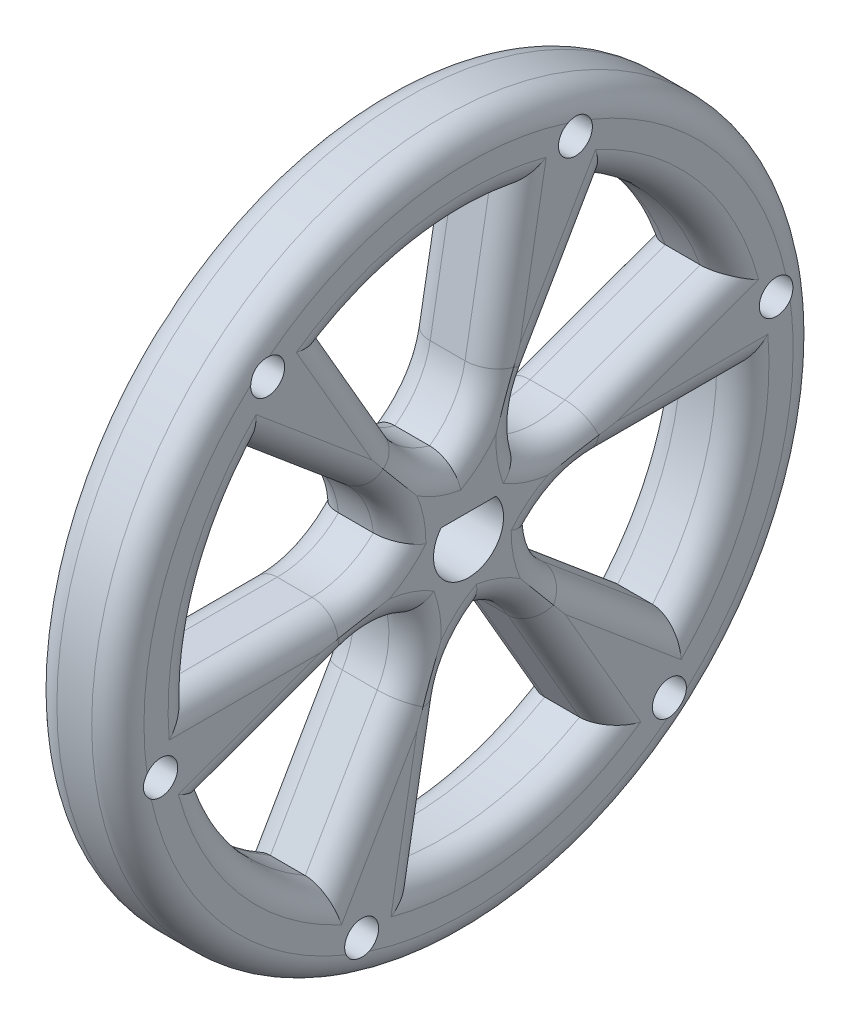
SolidWorks part; units mm, degrees
ref_plane "Front Plane" through (0, 0, 0) normal (0, 0, 1) x (1, 0, 0)
ref_plane "Top Plane" through (0, 0, 0) normal (0, 1, 0) x (1, 0, 0)
ref_plane "Right Plane" through (0, 0, 0) normal (1, 0, 0) x (0, 0, -1)
sketch "Sketch1" plane through (0, 0, 0) normal (1, 0, 0) x (0, 0, -1)
  circle A0 centre (0, 0) radius 40.2714
extrude "Boss-Extrude1" add sketch "Sketch1" along normal blind 10
sketch "Sketch2" plane through (0, 0, 0) normal (-1, 0, 0) x (0, 0, 1)
  line L0 (3.1545, 2.5) -> (-3.1545, 2.5)
  circle A0 centre (0, 0) radius 4.025
  dimension "D1" = 8.05
  dimension "D2" = 2.5
extrude "Cut-Extrude1" cut sketch "Sketch2" against normal blind 10 contours L0 A0 region at (0, -0.4735, 0)
sketch "Sketch3" plane through (0, 0, 0) normal (-1, 0, 0) x (0, 0, 1)
  line L0 (8, 0) -> (31.5, 0)
  line L1 (29.6003, -10.7736) -> (7.5175, -2.7362)
  line L2 (4, -6.9282) -> (15.75, -27.2798)
  line L3 (5.4699, -31.0214) -> (1.3892, -7.8785)
  line L4 (-4, -6.9282) -> (-15.75, -27.2798)
  line L5 (-24.1304, -20.2478) -> (-6.1284, -5.1423)
  line L6 (-8, 0) -> (-31.5, 0)
  line L7 (-29.6003, 10.7736) -> (-7.5175, 2.7362)
  line L8 (-4, 6.9282) -> (-15.75, 27.2798)
  line L9 (-5.4699, 31.0214) -> (-1.3892, 7.8785)
  line L10 (4, 6.9282) -> (15.75, 27.2798)
  line L11 (24.1304, 20.2478) -> (6.1284, 5.1423)
  circle A0 centre (0, 0) radius 8
  circle A1 centre (0, 0) radius 31.5
  dimension "D1" = 63
  dimension "D2" = 16
  dimension "D3" = 20
  dimension "D4" = 6
extrude "Cut-Extrude2" cut sketch "Sketch3" against normal blind 10 contours L0 A1 L11 A0 | L2 A1 L1 A0 | L4 A1 L3 A0 | L6 A1 L5 A0 | L8 A1 L7 A0 | L10 A1 L9 A0 region at (0, 7.3994, 20.3298) region at (0, -13.9064, 16.573) region at (0, 21.3058, 3.7568) region at (0, -21.3058, -3.7568) region at (0, 13.9064, -16.573) region at (0, -7.3994, -20.3298)
fillet "Fillet1" radius 10 12 edges at (5, 6.9282, -4) (5, 2.7362, -7.5175) (5, 0, -8) (5, -5.1423, -6.1284) (5, -6.9282, -4) (5, -7.8785, 1.3892) (5, 6.9282, 4) (5, 7.8785, -1.3892) (5, 5.1423, 6.1284) (5, 0, 8) (5, -2.7362, 7.5175) (5, -6.9282, 4)
fillet "Fillet3" radius 3 30 edges at (0, -6.6028, -9.0361) (0, -0.7503, -11.1663) (0, 4.5241, -10.2363) (0, 9.2951, -6.2329) (0, 11.1269, -1.2001) (0, 10.0454, 4.9334) (0, 14.9341, 17.7978) (0, 0.7503, 11.1663) (0, -4.5241, 10.2363) (0, -9.2951, 6.2329) (0, -10.7736, -29.6003) (0, -14.9341, -17.7978) (0, 0, -23.2333) (0, 7.9463, -21.8322) (0, 20.1206, -11.6167) (0, 20.2478, -24.1304) (0, 31.0214, 5.4699) (0, 22.8803, -4.0344) (0, 20.1206, 11.6167) (0, 10.7736, 29.6003) (0, 6.6028, 9.0361) (0, 0, 23.2333) (0, -7.9463, 21.8322) (0, -20.2478, 24.1304) (0, -20.1206, 11.6167) (0, -10.0454, -4.9334) (0, -20.1206, -11.6167) (0, -31.0214, -5.4699) (0, -11.1269, 1.2001) (0, -22.8803, 4.0344)
fillet "Fillet4" radius 3 32 edges at (10, 20.1206, -11.6167) (10, 4.5241, -10.2363) (10, 22.8803, -4.0344) (10, 10.0454, 4.9334) (10, 6.6028, 9.0361) (10, 0.7503, 11.1663) (10, -4.5241, 10.2363) (10, -11.1269, 1.2001) (10, -10.0454, -4.9334) (10, -6.6028, -9.0361) (10, -0.7503, -11.1663) (10, 31.0214, 5.4699) (10, 20.2478, -24.1304) (10, 9.2951, -6.2329) (10, 7.9463, -21.8322) (10, 11.1269, -1.2001) (10, 20.1206, 11.6167) (10, 14.9341, 17.7978) (10, 10.7736, 29.6003) (10, 0, 23.2333) (10, -7.9463, 21.8322) (10, -20.2478, 24.1304) (10, -22.8803, 4.0344) (10, -31.0214, -5.4699) (10, -20.1206, -11.6167) (10, -10.7736, -29.6003) (10, -14.9341, -17.7978) (10, 0, -23.2333) (10, -9.2951, 6.2329) (10, -20.1206, 11.6167) (0, 0, -40.2714) (10, 0, -40.2714)
sketch "Sketch4" plane through (0, 0, 0) normal (-1, 0, 0) x (0, 0, 1)
  line L0 (0, 0) -> (-11.105, -13.2344) construction
  line L1 (-11.105, -13.2344) -> (-25.886, -30.8497) construction
  line L2 (-25.886, -30.8497) -> (-27.0869, -30.2167) construction
  circle A0 centre (-23.0664, -27.4895) radius 3.5
  circle A2 centre (0, 0) radius 40.2714 construction
  circle A3 centre (0, 0) radius 37.2714 construction
  point P5 (-22.7833, -27.152)
  point P14 (-22.8821, -27.2698)
  dimension "D1" = 7
  dimension "D3" = 35.885
extrude "Cut-Extrude3" cut sketch "Sketch4" against normal blind 2
sketch "Sketch5" plane through (2, 0, 0) normal (-1, 0, 0) x (0, 0, 1)
  circle A0 centre (-23.0664, -27.4895) radius 1.95
  arc A1 (-26.3716, -26.3381) -> (-21.3586, -30.5445) centre (-23.0664, -27.4895) ccw construction
  dimension "D1" = 3.9
extrude "Cut-Extrude4" cut sketch "Sketch5" against normal up to next
pattern_circular "CirPattern1" count 6 over 360 about axis through (10, 0, 0) along (-1, 0, 0) of "Cut-Extrude3", "Cut-Extrude4"
